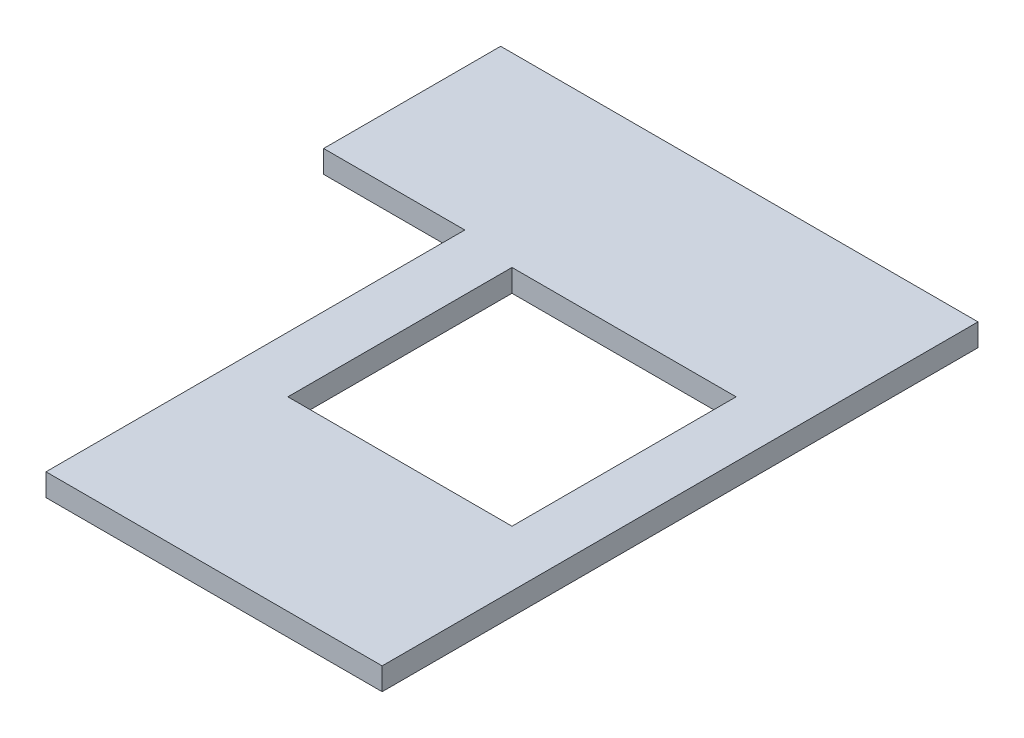
SolidWorks part; units mm, degrees
ref_plane "Front Plane" through (0, 0, 0) normal (0, 0, 1) x (1, 0, 0)
ref_plane "Top Plane" through (0, 0, 0) normal (0, 1, 0) x (1, 0, 0)
ref_plane "Right Plane" through (0, 0, 0) normal (1, 0, 0) x (0, 0, -1)
sketch "Sketch1" plane through (0, 0, 0) normal (0, 1, 0) x (1, 0, 0)
  line L1 (0, 0) -> (-150, 0)
  line L2 (0, 0) -> (0, 30)
  line L3 (0, 30) -> (-150, 30)
  line L4 (-150, 0) -> (-150, 30)
  dimension "D1" = 30
  dimension "D2" = 150
extrude "Boss-Extrude1" add sketch "Sketch1" along normal blind 10
sketch "Sketch8" plane through (0, 0, 0) normal (0, -1, 0) x (-1, 0, 0)
  line L0 (150, 0) -> (0, 30)
  line L1 (150, 30) -> (0, 0)
  line L2 (150, 0) -> (0, 0) construction
sketch "Sketch9" plane through (0, 0, 0) normal (0, -1, 0) x (1, 0, 0)
  line L0 (-150, -30) -> (0, 0) construction
  line L1 (0, -147.94) -> (-150, -147.94)
  line L2 (0, -147.94) -> (0, 117.94)
  line L3 (0, 117.94) -> (-150, 117.94)
  line L4 (-150, -147.94) -> (-150, 117.94)
  line L5 (0, -147.94) -> (-150, 117.94) construction
  line L6 (0, 117.94) -> (-150, -147.94) construction
  line L8 (-125, -65) -> (-25, -65)
  line L9 (-125, -65) -> (-125, 35)
  line L10 (-125, 35) -> (-25, 35)
  line L11 (-25, -65) -> (-25, 35)
  line L12 (-125, -65) -> (-25, 35) construction
  line L13 (-125, 35) -> (-25, -65) construction
  point P0 (-75, -15)
  point P7 (-75, -15)
  point P12 (-75, 117.94)
  point P13 (-75, -147.94)
  dimension "D1" = 265.88
  dimension "D2" = 150
  dimension "D3" = 100
  dimension "D4" = 100
extrude "Boss-Extrude3" add sketch "Sketch9" along normal blind 10
sketch "Sketch25" plane through (0, 0, 0) normal (0, 1, 0) x (1, 0, 0)
  line L1 (0, 30) -> (-150, 30)
  line L2 (0, 30) -> (0, 0)
  line L3 (0, 0) -> (-150, 0)
  line L4 (-150, 30) -> (-150, 0)
extrude "Cut-Extrude2" cut sketch "Sketch25" along normal blind 10
sketch "Alignment Sketch" plane through (0, 0, 0) normal (0, 1, 0) x (1, 0, 0)
  line L0 (-150, 147.94) -> (0, 147.94) construction
  line L1 (0, 147.94) -> (0, -117.94) construction
  point P0 (-75, 147.94)
  point P1 (0, 15)
sketch "Alignment Sketch 2" plane through (0, 0, -147.94) normal (0, 0, -1) x (-1, 0, 0)
  line L0 (75, 0) -> (75, -10) construction
  line L1 (150, -10) -> (0, -10) construction
sketch "Sketch26" plane through (-150, 0, 0) normal (-1, 0, 0) x (0, 0, 1)
  line L0 (117.94, -10) -> (-147.94, -10) construction
  line L1 (-147.94, 0) -> (-68.94, 0)
  line L2 (-147.94, 0) -> (-147.94, -10)
  line L3 (-147.94, -10) -> (-68.94, -10)
  line L4 (-68.94, 0) -> (-68.94, -10)
  dimension "D1" = 79
extrude "Boss-Extrude4" add sketch "Sketch26" along normal blind 63
